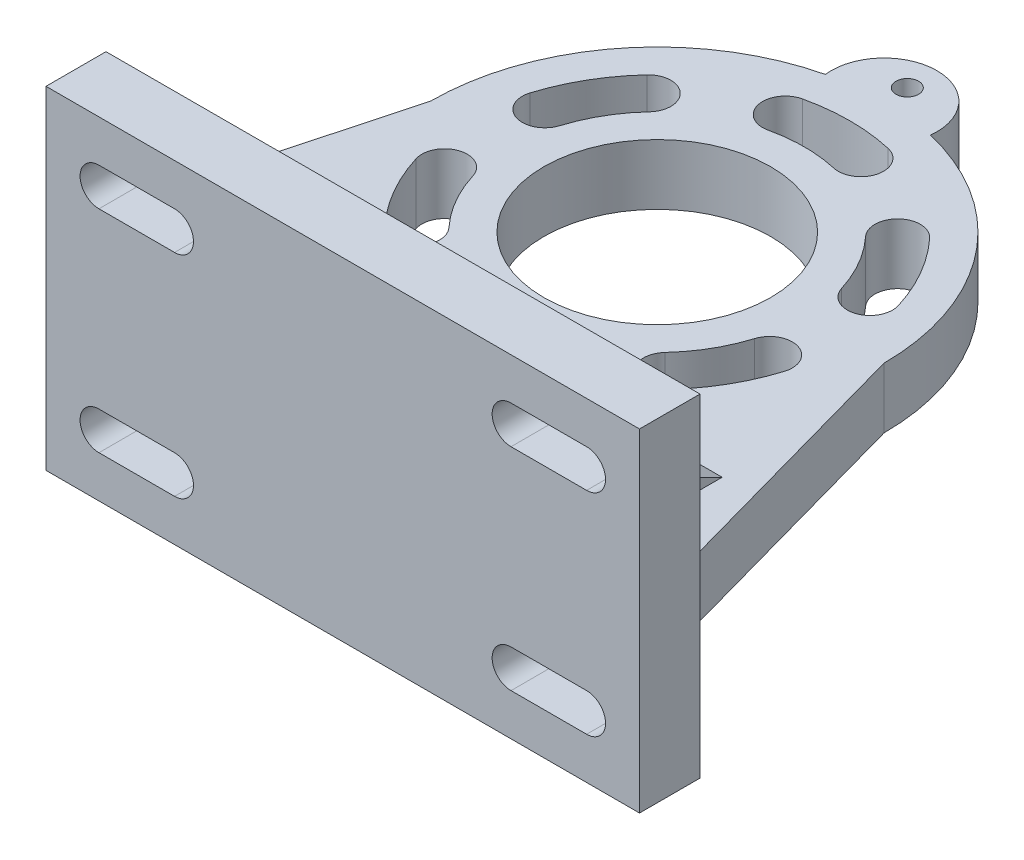
SolidWorks part; units mm, degrees
ref_plane "Front Plane" through (0, 0, 0) normal (0, 0, 1) x (1, 0, 0)
ref_plane "Top Plane" through (0, 0, 0) normal (0, 1, 0) x (1, 0, 0)
ref_plane "Right Plane" through (0, 0, 0) normal (1, 0, 0) x (0, 0, -1)
sketch "Sketch1" plane through (0, 0, 0) normal (0, 1, 0) x (1, 0, 0)
  circle A0 centre (0, 0) radius 30
  dimension "D1" = 60
extrude "Boss-Extrude1" add sketch "Sketch1" along normal blind 8 contours A0
sketch "Sketch10" plane through (0, 8, 0) normal (0, 1, 0) x (1, 0, 0)
  arc A0 (5, 21.9374) -> (-5, 21.9374) centre (0, 0) ccw construction
  arc A1 (5.6667, 24.8624) -> (-5.6667, 24.8624) centre (0, 0) ccw
  arc A2 (4.3333, 19.0124) -> (-4.3333, 19.0124) centre (0, 0) ccw
  arc A3 (4.3333, 19.0124) -> (5.6667, 24.8624) centre (5, 21.9374) ccw
  arc A4 (-5.6667, 24.8624) -> (-4.3333, 19.0124) centre (-5, 21.9374) ccw
  arc A5 (21.4984, 6.6386) -> (16.4984, 15.2988) centre (0, 0) ccw construction
  arc A6 (24.3648, 7.5237) -> (18.6981, 17.3387) centre (0, 0) ccw
  arc A7 (18.6319, 5.7534) -> (14.2986, 13.259) centre (0, 0) ccw
  arc A8 (18.6319, 5.7534) -> (24.3648, 7.5237) centre (21.4984, 6.6386) ccw
  arc A9 (18.6981, 17.3387) -> (14.2986, 13.259) centre (16.4984, 15.2988) ccw
  arc A10 (16.4984, -15.2988) -> (21.4984, -6.6386) centre (0, 0) ccw construction
  arc A11 (18.6981, -17.3387) -> (24.3648, -7.5237) centre (0, 0) ccw
  arc A12 (14.2986, -13.259) -> (18.6319, -5.7534) centre (0, 0) ccw
  arc A13 (14.2986, -13.259) -> (18.6981, -17.3387) centre (16.4984, -15.2988) ccw
  arc A14 (24.3648, -7.5237) -> (18.6319, -5.7534) centre (21.4984, -6.6386) ccw
  arc A15 (-5, -21.9374) -> (5, -21.9374) centre (0, 0) ccw construction
  arc A16 (-5.6667, -24.8624) -> (5.6667, -24.8624) centre (0, 0) ccw
  arc A17 (-4.3333, -19.0124) -> (4.3333, -19.0124) centre (0, 0) ccw
  arc A18 (-4.3333, -19.0124) -> (-5.6667, -24.8624) centre (-5, -21.9374) ccw
  arc A19 (5.6667, -24.8624) -> (4.3333, -19.0124) centre (5, -21.9374) ccw
  arc A20 (-21.4984, -6.6386) -> (-16.4984, -15.2988) centre (0, 0) ccw construction
  arc A21 (-24.3648, -7.5237) -> (-18.6981, -17.3387) centre (0, 0) ccw
  arc A22 (-18.6319, -5.7534) -> (-14.2986, -13.259) centre (0, 0) ccw
  arc A23 (-18.6319, -5.7534) -> (-24.3648, -7.5237) centre (-21.4984, -6.6386) ccw
  arc A24 (-18.6981, -17.3387) -> (-14.2986, -13.259) centre (-16.4984, -15.2988) ccw
  arc A25 (-16.4984, 15.2988) -> (-21.4984, 6.6386) centre (0, 0) ccw construction
  arc A26 (-18.6981, 17.3387) -> (-24.3648, 7.5237) centre (0, 0) ccw
  arc A27 (-14.2986, 13.259) -> (-18.6319, 5.7534) centre (0, 0) ccw
  arc A28 (-14.2986, 13.259) -> (-18.6981, 17.3387) centre (-16.4984, 15.2988) ccw
  arc A29 (-24.3648, 7.5237) -> (-18.6319, 5.7534) centre (-21.4984, 6.6386) ccw
  circle A30 centre (0, 0) radius 15
  point P5 (0, 22.5)
  point P12 (19.4856, 11.25)
  point P19 (19.4856, -11.25)
  point P26 (0, -22.5)
  point P34 (-19.4856, -11.25)
  point P41 (-19.4856, 11.25)
  point P46 (0, 0)
  dimension "D4" = 6
  dimension "D3" = 10
  dimension "D2" = 22.5
  dimension "D1" = 3
  dimension "D5" = 30
extrude "Cut-Extrude3" cut sketch "Sketch10" against normal blind 10
sketch "Sketch11" plane through (0, 8, 0) normal (0, 1, 0) x (1, 0, 0)
  line L0 (-30, 0) -> (-30, -30)
  line L1 (-30, -30) -> (30, -30)
  line L2 (30, 0) -> (30, -30)
  circle A0 centre (0, 0) radius 30 construction
sketch "Sketch12" plane through (0, 8, 0) normal (0, 1, 0) x (1, 0, 0)
  line L3 (-30, 0) -> (-39.1321, -33.7876)
  line L4 (-39.1321, -33.7876) -> (39.374, -33.7213)
  line L5 (30, 0) -> (39.374, -33.7213)
  circle A2 centre (0, 0) radius 30 construction
  circle A3 centre (0, 0) radius 30
  circle M27 centre (0, 0) radius 30
  dimension "D1" = 35
  dimension "D2" = 35
extrude "Boss-Extrude2" add sketch "Sketch12" against normal blind 8 contours M27 | M27 region at (0, 8, 30.8547)
sketch "Sketch13" plane through (0, 8, 0) normal (0, 1, 0) x (1, 0, 0)
  line L6 (-39.1321, -33.7876) -> (39.374, -33.7213)
  line L8 (-39.1321, -41.7213) -> (39.374, -41.7213)
  line L10 (-39.1321, -33.7876) -> (-39.1321, -41.7213)
  line L12 (39.374, -33.7213) -> (39.374, -41.7213)
  dimension "D1" = 8
extrude "Boss-Extrude3" add sketch "Sketch13" along normal blind 18 and the other way blind 26
ref_plane "Plane1" through (-29.1321, 0, 0) normal (-1, 0, 0) x (0, 0, 1)
sketch "Sketch15" plane through (-29.1321, 0, 0) normal (-1, 0, 0) x (0, 0, 1)
  line L5 (23.7876, 8) -> (33.7876, 13)
  line L6 (0, 8) -> (33.7876, 8) construction
  line L7 (33.7876, 8) -> (33.7876, 26) construction
  dimension "D1" = 5
  dimension "D2" = 10
rib "Rib22" sketch "Sketch15" sketch "Sketch15" thickness 6 extrusion direction parallel to sketch draft on no parameters "D1"=6
ref_plane "Plane2" through (0.1209, 0, 0) normal (-1, 0, 0) x (0, 0, 1)
mirror "Mirror1" about plane through (0.1209, 0, 0) normal (-1, 0, 0) of "Rib22"
ref_plane "Plane3" through (0, 4, 0) normal (0, 1, 0) x (1, 0, 0)
mirror "Mirror2" about plane through (0, 4, 0) normal (0, 1, 0) of "Mirror1", "Rib22"
sketch "Sketch16" plane through (0, 8, 0) normal (0, 1, 0) x (1, 0, 0)
  arc A5 (6.9522, 29.1833) -> (-6.9522, 29.1833) centre (0, 30) ccw
  arc A6 (30, 0) -> (-30, 0) centre (0, 0) ccw construction
  circle A7 centre (0, 33.0745) radius 1.5
  arc A8 (6.9522, 29.1833) -> (-6.9522, 29.1833) centre (0, 0) ccw
  dimension "D1" = 14
  dimension "D2" = 3
extrude "Boss-Extrude4" add sketch "Sketch16" against normal blind 8
sketch "Sketch17" plane through (0.0285, 0, 33.7546) normal (-0.0008, 0, -1) x (-1, 0, 0.0008)
  line L0 (-32.3455, 17.9698) -> (-22.3455, 17.9698) construction
  line L1 (-32.3455, 20.4698) -> (-22.3455, 20.4698)
  line L2 (-32.3455, 15.4698) -> (-22.3455, 15.4698)
  line L3 (-32.3455, 15.4698) -> (-32.3455, 12.9421) construction
  line L5 (-0.0924, 26) -> (-0.0924, 15.4698) construction
  line L8 (-32.3455, 12.9698) -> (-32.3455, 8) construction
  line L11 (-39.3455, 26) -> (39.1607, 26) construction
  line L14 (-39.3455, 4) -> (-32.9188, 4) construction
  line L17 (-26.3455, 12.9723) -> (-32.3455, 12.9698) construction
  line L18 (-39.3455, 0) -> (-39.3455, 8) construction
  line L19 (4.4, 4) -> (-4.4, 4) construction
  line L20 (32.1607, 17.9698) -> (22.1607, 17.9698) construction
  line L21 (32.1607, 20.4698) -> (22.1607, 20.4698)
  line L22 (32.1607, 15.4698) -> (22.1607, 15.4698)
  line L23 (32.1607, -9.9698) -> (22.1607, -9.9698) construction
  line L24 (32.1607, -12.4698) -> (22.1607, -12.4698)
  line L25 (32.1607, -7.4698) -> (22.1607, -7.4698)
  line L26 (-32.3455, -9.9698) -> (-22.3455, -9.9698) construction
  line L27 (-32.3455, -12.4698) -> (-22.3455, -12.4698)
  line L28 (-32.3455, -7.4698) -> (-22.3455, -7.4698)
  arc A0 (-32.3455, 20.4698) -> (-32.3455, 15.4698) centre (-32.3455, 17.9698) ccw
  arc A1 (-22.3455, 15.4698) -> (-22.3455, 20.4698) centre (-22.3455, 17.9698) ccw
  arc A8 (32.1607, 20.4698) -> (32.1607, 15.4698) centre (32.1607, 17.9698) cw
  arc A9 (22.1607, 15.4698) -> (22.1607, 20.4698) centre (22.1607, 17.9698) cw
  arc A10 (32.1607, -12.4698) -> (32.1607, -7.4698) centre (32.1607, -9.9698) ccw
  arc A11 (22.1607, -7.4698) -> (22.1607, -12.4698) centre (22.1607, -9.9698) ccw
  arc A12 (-32.3455, -12.4698) -> (-32.3455, -7.4698) centre (-32.3455, -9.9698) cw
  arc A13 (-22.3455, -7.4698) -> (-22.3455, -12.4698) centre (-22.3455, -9.9698) cw
  point P2 (-27.3455, 17.9698)
  point P25 (27.1607, 17.9698)
  point P32 (27.1607, -9.9698)
  point P39 (-27.3455, -9.9698)
  dimension "D2" = 2.5
  dimension "D1" = 10
  dimension "D3" = 0
  dimension "D4" = 5
extrude "Cut-Extrude4" cut sketch "Sketch17" against normal blind 8
